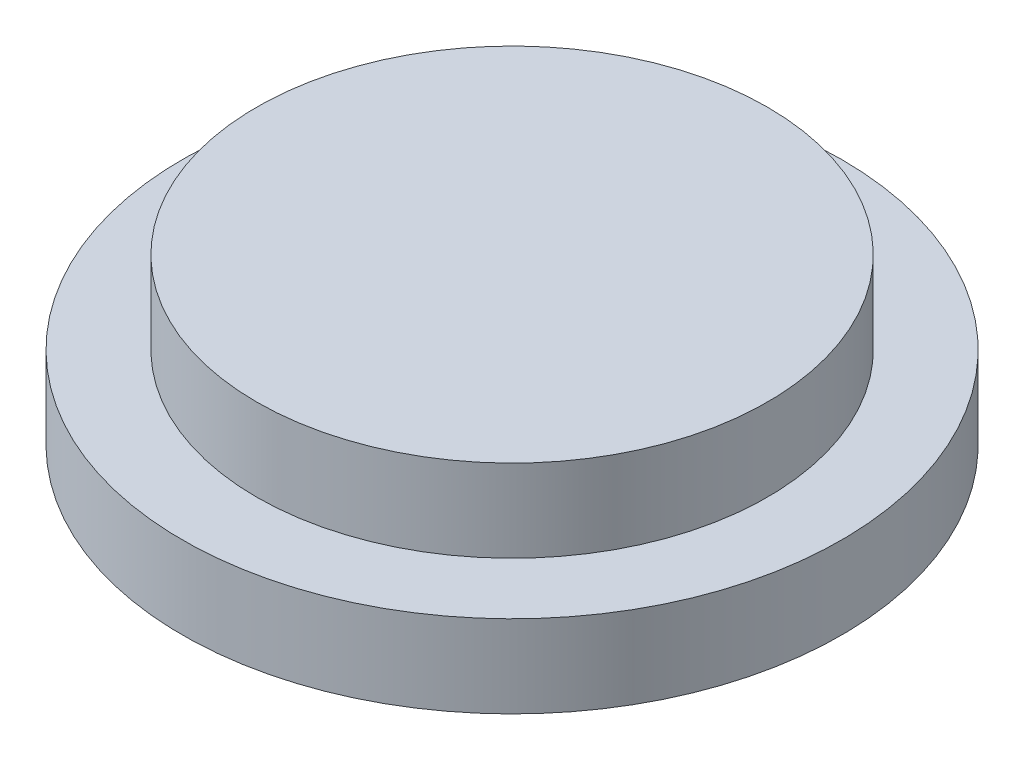
SolidWorks part; units mm, degrees
material "PBT General Purpose"
ref_plane "Front Plane" through (0, 0, 0) normal (0, 0, 1) x (1, 0, 0)
ref_plane "Top Plane" through (0, 0, 0) normal (0, 1, 0) x (1, 0, 0)
ref_plane "Right Plane" through (0, 0, 0) normal (1, 0, 0) x (0, 0, -1)
sketch "Sketch1" plane through (0, 0, 0) normal (0, 1, 0) x (1, 0, 0)
  circle A0 centre (0, 0) radius 31
extrude "Boss-Extrude1" add sketch "Sketch1" along normal blind 10
sketch "Sketch6" plane through (0, 0, 0) normal (0, -1, 0) x (-1, 0, 0)
  line L0 (0, 0) -> (15, 0) construction
  line L1 (0, 0) -> (-15, 0) construction
  line L2 (15, 0) -> (15, -10)
  line L3 (15, -10) -> (-15, -10)
  line L4 (-15, -10) -> (-15, 0)
  line L5 (-15, 0) -> (-15, 10)
  line L6 (-15, 10) -> (15, 10)
  line L7 (15, 10) -> (15, 0)
extrude "Boss-Extrude3" add sketch "Sketch6" along normal blind 10
sketch "Sketch7" plane through (0, 0, -10) normal (0, 0, -1) x (-1, 0, 0)
  line L0 (0, 0) -> (0, -10) construction
  line L1 (15, -10) -> (-15, -10) construction
  line L2 (10, -5) -> (5, -5)
  line L3 (10, -5) -> (15, -10)
  line L4 (5, -5) -> (5, 0)
  line L5 (15, 0) -> (-15, 0) construction
  line L6 (5, 0) -> (15, 0)
  line L7 (15, 0) -> (15, -10)
  line L8 (-5, 0) -> (-15, 0)
  line L9 (-5, -5) -> (-5, 0)
  line L10 (-10, -5) -> (-15, -10)
  line L11 (-10, -5) -> (-5, -5)
  line L12 (-15, 0) -> (-15, -10)
extrude "Cut-Extrude2" cut sketch "Sketch7" against normal through all
sketch "Sketch8" plane through (0, 0, 0) normal (0, -1, 0) x (1, 0, 0)
  line L0 (15, -10) -> (22.5, -10)
  line L1 (-15, -10) -> (-22.5, -10)
  line L3 (15, 10) -> (22.5, 10)
  line L4 (22.5, 10) -> (22.5, -10)
  line L5 (-22.5, -10) -> (-22.5, 10)
  line L6 (-22.5, 10) -> (-15, 10)
  line L7 (15, 10) -> (-15, 10)
  line L8 (15, -10) -> (-15, -10)
  circle A0 centre (0, 0) radius 40
extrude "Boss-Extrude4" add sketch "Sketch8" along normal blind 10
